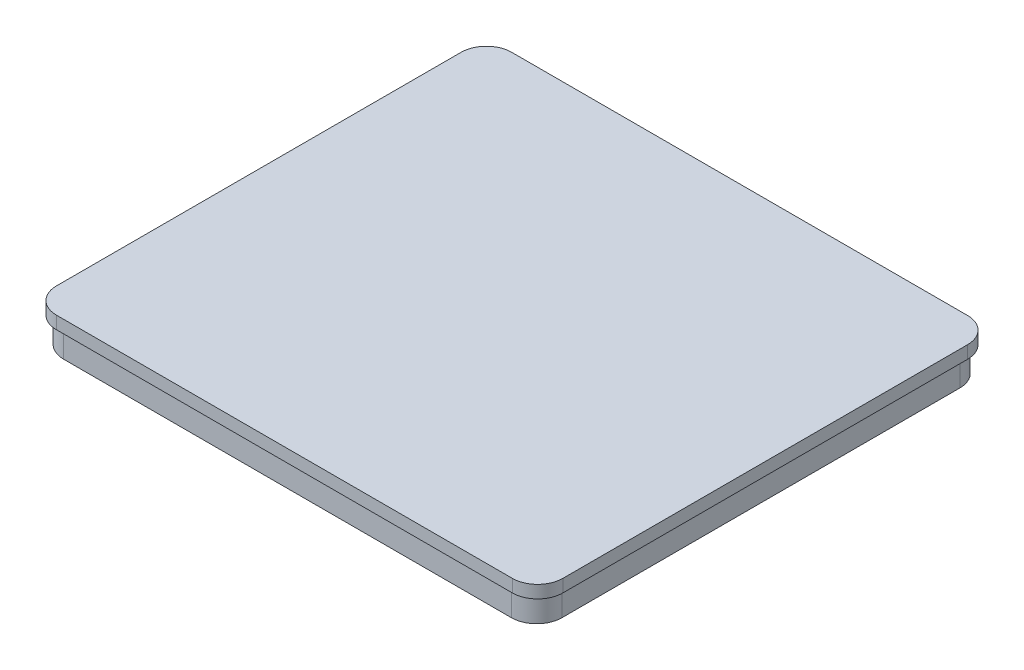
SolidWorks part; units mm, degrees
ref_plane "Front Plane" through (0, 0, 0) normal (0, 0, 1) x (1, 0, 0)
ref_plane "Top Plane" through (0, 0, 0) normal (0, 1, 0) x (1, 0, 0)
ref_plane "Right Plane" through (0, 0, 0) normal (1, 0, 0) x (0, 0, -1)
sketch "Sketch1" plane through (0, 0, 0) normal (0, 1, 0) x (1, 0, 0)
  line L1 (-64.4802, 42.5321) -> (115.9529, 42.5321)
  line L2 (-74.4802, 32.5321) -> (-74.4802, -127.6341)
  line L3 (-64.4802, -137.6341) -> (115.9529, -137.6341)
  line L4 (125.9529, 32.5321) -> (125.9529, -127.6341)
  arc A0 (125.9529, -127.6341) -> (115.9529, -137.6341) centre (115.9529, -127.6341) cw
  arc A1 (-64.4802, -137.6341) -> (-74.4802, -127.6341) centre (-64.4802, -127.6341) cw
  arc A2 (125.9529, 32.5321) -> (115.9529, 42.5321) centre (115.9529, 32.5321) ccw
  arc A3 (-64.4802, 42.5321) -> (-74.4802, 32.5321) centre (-64.4802, 32.5321) ccw
  dimension "D1" = 10
extrude "Boss-Extrude1" add sketch "Sketch1" along normal blind 5
sketch "Sketch2" plane through (0, 5, 0) normal (0, 1, 0) x (1, 0, 0)
  line L1 (-62.9282, 41.1236) -> (114.272, 41.1236)
  line L2 (-72.9282, 31.1236) -> (-72.9282, -126.32)
  line L3 (-62.9282, -136.32) -> (114.272, -136.32)
  line L4 (124.272, 31.1236) -> (124.272, -126.32)
  line L5 (-59.2696, 37.0991) -> (109.8816, 37.0991)
  line L6 (-69.2696, 27.0991) -> (-69.2696, -121.9296)
  line L7 (-59.2696, -131.9296) -> (109.8816, -131.9296)
  line L8 (119.8816, 27.0991) -> (119.8816, -121.9296)
  arc A0 (109.8816, -131.9296) -> (119.8816, -121.9296) centre (109.8816, -121.9296) ccw
  arc A1 (119.8816, 27.0991) -> (109.8816, 37.0991) centre (109.8816, 27.0991) ccw
  arc A2 (-59.2696, 37.0991) -> (-69.2696, 27.0991) centre (-59.2696, 27.0991) ccw
  arc A3 (-59.2696, -131.9296) -> (-69.2696, -121.9296) centre (-59.2696, -121.9296) cw
  arc A4 (-72.9282, -126.32) -> (-62.9282, -136.32) centre (-62.9282, -126.32) ccw
  arc A5 (114.272, -136.32) -> (124.272, -126.32) centre (114.272, -126.32) ccw
  arc A6 (124.272, 31.1236) -> (114.272, 41.1236) centre (114.272, 31.1236) ccw
  arc A7 (-62.9282, 41.1236) -> (-72.9282, 31.1236) centre (-62.9282, 31.1236) ccw
  dimension "D1" = 10
extrude "Boss-Extrude2" add sketch "Sketch2" against normal blind 15
sketch "Sketch3" plane through (119.8816, 0, 0) normal (-1, 0, 0) x (0, 0, 1)
  text T0 "<b>designed by wedeloe@gmail.com</b>"
extrude "Cut-Extrude1" cut sketch "Sketch3" against normal blind 0.8
